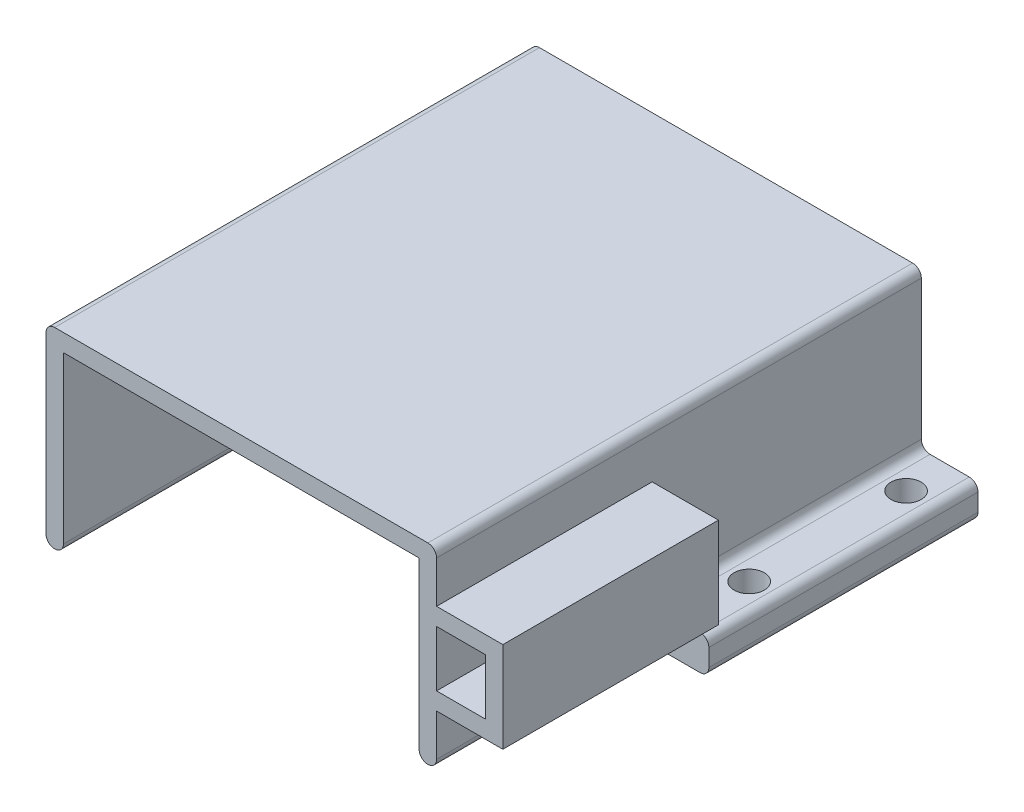
SolidWorks part; units mm, degrees
ref_plane "Front Plane" through (0, 0, 0) normal (0, 0, 1) x (1, 0, 0)
ref_plane "Top Plane" through (0, 0, 0) normal (0, 1, 0) x (1, 0, 0)
ref_plane "Right Plane" through (0, 0, 0) normal (1, 0, 0) x (0, 0, -1)
sketch "Sketch1" plane through (0, 0, 0) normal (0, 0, 1) x (1, 0, 0)
  line L0 (0, 0) -> (0, 25.4) construction
  line L1 (25.908, 25.4) -> (-25.908, 25.4)
  line L2 (-25.908, 25.4) -> (-25.908, 0)
  line L3 (-25.908, 0) -> (-36.703, 0)
  line L4 (-36.703, 0) -> (-36.703, 5.08)
  line L5 (-36.703, 5.08) -> (-28.448, 5.08)
  line L6 (-28.448, 5.08) -> (-28.448, 27.94)
  line L7 (-28.448, 27.94) -> (28.448, 27.94)
  line L9 (28.448, 5.08) -> (28.448, 27.94)
  line L10 (36.703, 5.08) -> (28.448, 5.08)
  line L11 (36.703, 0) -> (36.703, 5.08)
  line L12 (25.908, 0) -> (36.703, 0)
  line L13 (25.908, 25.4) -> (25.908, 0)
  point P6 (0, 25.4)
  point P12 (0, 27.94)
  dimension "D1" = 25.4
  dimension "D2" = 25.908
  dimension "D3" = 5.08
  dimension "D4" = 2.54
  dimension "D5" = 36.703
  dimension "D6" = 2.54
extrude "Boss-Extrude1" add sketch "Sketch1" along normal blind 70.612
sketch "Sketch2" plane through (0, 5.08, 0) normal (0, 1, 0) x (1, 0, 0)
  line L0 (-28.448, 0) -> (-36.703, 0) construction
  line L1 (-32.5755, 0) -> (-32.5755, -70.612) construction
  line L2 (-28.448, -70.612) -> (-36.703, -70.612) construction
  circle A0 centre (-32.5755, -6.35) radius 2.2
  circle A1 centre (-32.5755, -29.21) radius 2.2
  point P12 (0, 0)
  dimension "D1" = 4.4
  dimension "D3" = 22.86
  dimension "D4" = 6.35
extrude "Cut-Extrude1" cut sketch "Sketch2" against normal through all
mirror "Mirror1" about plane through (0, 0, 0) normal (1, 0, 0) of "Cut-Extrude1"
sketch "Sketch3" plane through (0, 5.08, 0) normal (0, 1, 0) x (1, 0, 0)
  line L0 (-36.703, -39.2106) -> (-28.448, -39.2106)
  line L1 (-36.703, -70.612) -> (-36.703, 0) construction
  line L2 (-28.448, -70.612) -> (-28.448, 0) construction
  line L3 (-28.448, -39.2106) -> (-28.448, -70.612)
  line L4 (-28.448, -70.612) -> (-36.703, -70.612)
  line L5 (-36.703, -70.612) -> (-36.703, -39.2106)
  line L6 (0, 0) -> (0, -70.612) construction
  line L7 (28.448, -70.612) -> (-28.448, -70.612) construction
  line L8 (36.703, -70.612) -> (36.703, -39.2106)
  line L9 (28.448, -70.612) -> (36.703, -70.612)
  line L10 (28.448, -39.2106) -> (28.448, -70.612)
  line L11 (36.703, -39.2106) -> (28.448, -39.2106)
extrude "Cut-Extrude2" cut sketch "Sketch3" against normal through all
sketch "Sketch6" plane through (0, 0, 0) normal (0, 0, -1) x (-1, 0, 0)
  line L0 (-25.908, 0) -> (25.908, 0)
  line L16 (25.908, 25.4) -> (25.908, 0)
  line L17 (25.908, 0) -> (36.703, 0)
  line L18 (36.703, 0) -> (36.703, 5.08)
  line L19 (36.703, 5.08) -> (28.448, 5.08)
  line L20 (28.448, 5.08) -> (28.448, 27.94)
  line L21 (28.448, 27.94) -> (-28.448, 27.94)
  line L22 (-28.448, 27.94) -> (-28.448, 5.08)
  line L23 (-28.448, 5.08) -> (-36.703, 5.08)
  line L24 (-36.703, 5.08) -> (-36.703, 0)
  line L25 (-36.703, 0) -> (-25.908, 0)
  line L26 (-25.908, 0) -> (-25.908, 25.4)
  line L27 (-25.908, 25.4) -> (25.908, 25.4)
  line L29 (25.908, 0) -> (36.703, 0)
  line L30 (36.703, 0) -> (36.703, 5.08)
  line L31 (36.703, 5.08) -> (28.448, 5.08)
  line L32 (28.448, 5.08) -> (28.448, 27.94)
  line L33 (28.448, 27.94) -> (-28.448, 27.94)
  line L34 (-28.448, 27.94) -> (-28.448, 5.08)
  line L35 (-28.448, 5.08) -> (-36.703, 5.08)
  line L36 (-36.703, 5.08) -> (-36.703, 0)
  line L37 (-36.703, 0) -> (-25.908, 0)
  dimension "D1" = 0
extrude "Boss-Extrude3" add sketch "Sketch6" against normal blind 2.54
sketch "Sketch4" plane through (0, 0, 70.612) normal (0, 0, 1) x (1, 0, 0)
  line L1 (-28.448, 0) -> (28.448, 0)
  line L2 (-28.448, 0) -> (-28.448, 27.94)
  line L3 (-28.448, 27.94) -> (28.448, 27.94)
  line L4 (28.448, 0) -> (28.448, 27.94)
sketch "Sketch8" plane through (0, 0, 0) normal (0, 0, -1) x (-1, 0, 0)
  line L0 (-15.875, 0) -> (15.875, 0) construction
  line L1 (-15.875, 0) -> (15.875, 0)
  arc A0 (-15.875, 0) -> (15.875, 0) centre (0, -19.8279) cw
  point P0 (0, 0)
  dimension "D1" = 25.4
  dimension "D2" = 31.75
extrude "Cut-Extrude6" cut sketch "Sketch8" against normal up to surface (2.54 mm away) up to face at (0, 12.7, 2.54)
sketch "Sketch9" plane through (0, 0, 0) normal (0, 0, -1) x (-1, 0, 0)
  line L0 (25.908, 25.4) -> (25.908, 0) construction
  line L1 (-25.908, 0) -> (25.908, 0)
  line L2 (-25.908, 0) -> (-25.908, 2.54)
  line L3 (-25.908, 2.54) -> (25.908, 2.54)
  line L4 (25.908, 0) -> (25.908, 2.54)
  dimension "D1" = 2.54
extrude "Cut-Extrude7" cut sketch "Sketch9" against normal up to surface (2.54 mm away) up to face at (0, 9.3954, 2.54)
fillet "Fillet1" radius 1.27 12 edges at (-28.448, 5.08, 19.6053) (28.448, 5.08, 19.6053) (36.703, 0, 19.6053) (36.703, 5.08, 19.6053) (-36.703, 5.08, 19.6053) (-36.703, 0, 19.6053) (28.448, 0, 54.9113) (25.908, 0, 35.306) (-25.908, 0, 35.306) (-28.448, 0, 54.9113) (28.448, 27.94, 35.306) (-28.448, 27.94, 35.306)
fillet "Fillet2" radius 1.27 2 edges at (-25.908, 2.54, 1.27) (25.908, 2.54, 1.27)
sketch "Sketch10" plane through (0, 0, 70.612) normal (0, 0, 1) x (1, 0, 0)
  line L0 (28.448, 20.574) -> (38.1, 20.574)
  line L1 (28.448, 0) -> (28.448, 27.94) construction
  line L2 (38.1, 20.574) -> (38.1, 7.366)
  line L3 (38.1, 7.366) -> (28.448, 7.366)
  line L4 (28.448, 7.366) -> (28.448, 9.906)
  line L5 (28.448, 9.906) -> (35.56, 9.906)
  line L6 (35.56, 9.906) -> (35.56, 18.034)
  line L7 (35.56, 18.034) -> (28.448, 18.034)
  line L8 (28.448, 18.034) -> (28.448, 20.574)
  line L9 (0, 0) -> (0, 27.94) construction
  line L10 (-28.448, 27.94) -> (28.448, 27.94) construction
  point P15 (0, 13.97)
  point P16 (35.56, 13.97)
  dimension "D1" = 8.128
  dimension "D2" = 7.112
  dimension "D3" = 2.54
  dimension "D4" = 2.54
  dimension "D5" = 2.54
extrude "Boss-Extrude4" add sketch "Sketch10" against normal up to surface (31.4014 mm away) up to face at (32.3238, 2.7917, 39.2106)
